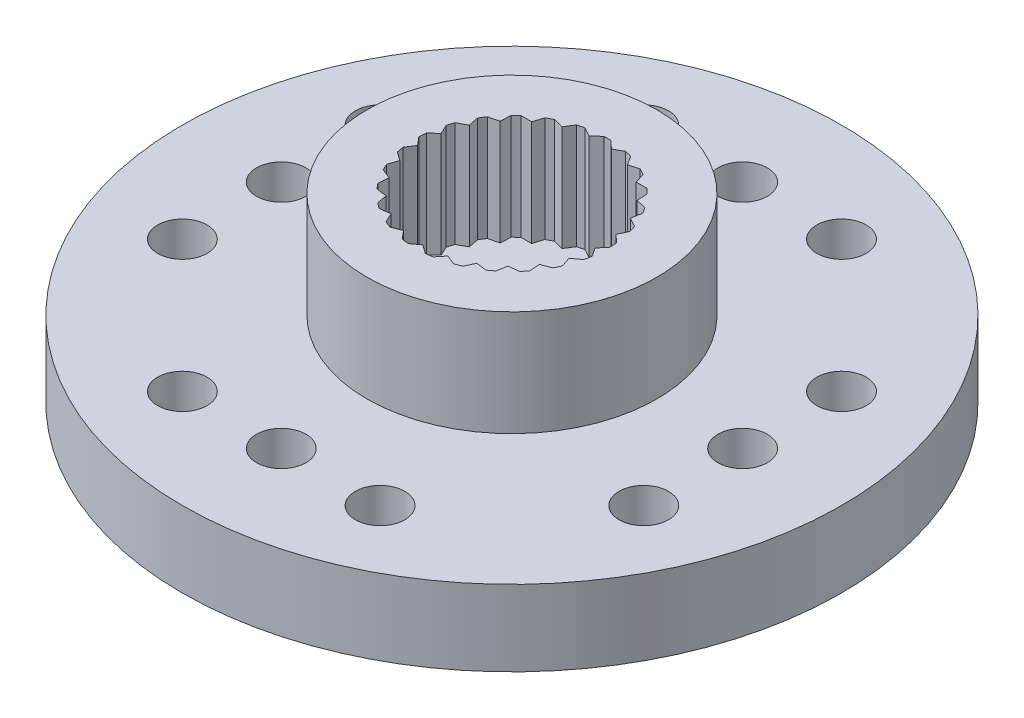
SolidWorks part; units mm, degrees
material "ABS"
ref_plane "Front Plane" through (0, 0, 0) normal (0, 0, 1) x (1, 0, 0)
ref_plane "Top Plane" through (0, 0, 0) normal (0, 1, 0) x (1, 0, 0)
ref_plane "Right Plane" through (0, 0, 0) normal (1, 0, 0) x (0, 0, -1)
sketch "Sketch2" plane through (0, 0, 0) normal (0, 1, 0) x (1, 0, 0)
  circle A0 centre (0, 0) radius 6
  circle A1 centre (0, 0) radius 1.5
  dimension "D1" = 12
  dimension "D2" = 3
extrude "Boss-Extrude1" add sketch "Sketch2" along normal mid plane 2.3
sketch "Sketch3" plane through (0, 1.15, 0) normal (0, 1, 0) x (1, 0, 0)
  line L0 (0, 0) -> (0, 2.9) construction
  line L3 (0, 0) -> (0.376, 2.9763) construction
  line L52 (0.1074, 2.898) -> (0.3384, 2.6787)
  line L53 (-0.1074, 2.898) -> (-0.3384, 2.6787)
  line L54 (0.8248, 2.7802) -> (0.9939, 2.5104)
  line L55 (0.6167, 2.8337) -> (0.3384, 2.6787)
  line L56 (1.4903, 2.4878) -> (1.587, 2.1843)
  line L57 (1.302, 2.5913) -> (0.9939, 2.5104)
  line L58 (2.0621, 2.039) -> (2.0804, 1.721)
  line L59 (1.9055, 2.1861) -> (1.587, 2.1843)
  line L60 (2.5044, 1.4621) -> (2.443, 1.1496)
  line L61 (2.3893, 1.6435) -> (2.0804, 1.721)
  line L62 (2.7894, 0.7934) -> (2.6522, 0.5059)
  line L63 (2.723, 0.9977) -> (2.443, 1.1496)
  line L64 (2.899, 0.0748) -> (2.6947, -0.1695)
  line L65 (2.8855, 0.2892) -> (2.6522, 0.5059)
  line L66 (2.8265, -0.6486) -> (2.5679, -0.8343)
  line L67 (2.8668, -0.4375) -> (2.6947, -0.1695)
  line L68 (2.5765, -1.3311) -> (2.2797, -1.4467)
  line L69 (2.6679, -1.1367) -> (2.5679, -0.8343)
  line L70 (2.1645, -1.93) -> (1.8483, -1.9682)
  line L71 (2.3014, -1.7645) -> (2.2797, -1.4467)
  line L72 (1.6165, -2.4077) -> (1.3007, -2.366)
  line L73 (1.7903, -2.2814) -> (1.8483, -1.9682)
  line L74 (0.967, -2.734) -> (0.6715, -2.6152)
  line L75 (1.1667, -2.655) -> (1.3007, -2.366)
  line L76 (0.2566, -2.8886) -> (0, -2.7)
  line L77 (0.4698, -2.8617) -> (0.6715, -2.6152)
  line L78 (-0.4698, -2.8617) -> (-0.6715, -2.6152)
  line L79 (-0.2566, -2.8886) -> (0, -2.7)
  line L80 (-1.1667, -2.655) -> (-1.3007, -2.366)
  line L81 (-0.967, -2.734) -> (-0.6715, -2.6152)
  line L82 (-1.7903, -2.2814) -> (-1.8483, -1.9682)
  line L83 (-1.6165, -2.4077) -> (-1.3007, -2.366)
  line L84 (-2.3014, -1.7645) -> (-2.2797, -1.4467)
  line L85 (-2.1645, -1.93) -> (-1.8483, -1.9682)
  line L86 (-2.6679, -1.1367) -> (-2.5679, -0.8343)
  line L87 (-2.5765, -1.3311) -> (-2.2797, -1.4467)
  line L88 (-2.8668, -0.4375) -> (-2.6947, -0.1695)
  line L89 (-2.8265, -0.6486) -> (-2.5679, -0.8343)
  line L90 (-2.8855, 0.2892) -> (-2.6522, 0.5059)
  line L91 (-2.899, 0.0748) -> (-2.6947, -0.1695)
  line L92 (-2.723, 0.9977) -> (-2.443, 1.1496)
  line L93 (-2.7894, 0.7934) -> (-2.6522, 0.5059)
  line L94 (-2.3893, 1.6435) -> (-2.0804, 1.721)
  line L95 (-2.5044, 1.4621) -> (-2.443, 1.1496)
  line L96 (-1.9055, 2.1861) -> (-1.587, 2.1843)
  line L97 (-2.0621, 2.039) -> (-2.0804, 1.721)
  line L98 (-1.302, 2.5913) -> (-0.9939, 2.5104)
  line L99 (-1.4903, 2.4878) -> (-1.587, 2.1843)
  line L100 (-0.6167, 2.8337) -> (-0.3384, 2.6787)
  line L101 (-0.8248, 2.7802) -> (-0.9939, 2.5104)
  line L102 (-2.533, 1.6075) -> (-2.3893, 1.6435) construction
  line L103 (-2.533, 1.6075) -> (-2.5044, 1.4621) construction
  line L104 (-2.8532, 0.9271) -> (-2.723, 0.9977) construction
  line L105 (-2.8532, 0.9271) -> (-2.7894, 0.7934) construction
  line L106 (-2.9941, 0.1884) -> (-2.8855, 0.2892) construction
  line L107 (-2.9941, 0.1884) -> (-2.899, 0.0748) construction
  line L108 (-2.9469, -0.5621) -> (-2.8668, -0.4375) construction
  line L109 (-2.9469, -0.5621) -> (-2.8265, -0.6486) construction
  line L110 (0, 3) -> (0.1074, 2.898) construction
  line L111 (0, 2.9) -> (0, 3) construction
  line L112 (0, 3) -> (-0.1074, 2.898) construction
  line L113 (-0.7461, 2.9057) -> (-0.6167, 2.8337) construction
  line L114 (-0.7461, 2.9057) -> (-0.8248, 2.7802) construction
  line L115 (-1.4453, 2.6289) -> (-1.302, 2.5913) construction
  line L116 (-1.4453, 2.6289) -> (-1.4903, 2.4878) construction
  line L117 (-2.0536, 2.1869) -> (-1.9055, 2.1861) construction
  line L118 (-2.0536, 2.1869) -> (-2.0621, 2.039) construction
  line L119 (-2.7145, -1.2773) -> (-2.6679, -1.1367) construction
  line L120 (-2.7145, -1.2773) -> (-2.5765, -1.3311) construction
  line L121 (-2.3115, -1.9123) -> (-2.3014, -1.7645) construction
  line L122 (-2.3115, -1.9123) -> (-2.1645, -1.93) construction
  line L123 (-1.7634, -2.4271) -> (-1.7903, -2.2814) construction
  line L124 (-1.7634, -2.4271) -> (-1.6165, -2.4077) construction
  line L125 (-1.1044, -2.7893) -> (-1.1667, -2.655) construction
  line L126 (-1.1044, -2.7893) -> (-0.967, -2.734) construction
  line L127 (-0.376, -2.9763) -> (-0.4698, -2.8617) construction
  line L128 (-0.376, -2.9763) -> (-0.2566, -2.8886) construction
  line L129 (0.376, -2.9763) -> (0.2566, -2.8886) construction
  line L130 (0.376, -2.9763) -> (0.4698, -2.8617) construction
  line L131 (1.1044, -2.7893) -> (0.967, -2.734) construction
  line L132 (1.1044, -2.7893) -> (1.1667, -2.655) construction
  line L133 (1.7634, -2.4271) -> (1.6165, -2.4077) construction
  line L134 (1.7634, -2.4271) -> (1.7903, -2.2814) construction
  line L135 (2.3115, -1.9123) -> (2.3014, -1.7645) construction
  line L136 (2.3115, -1.9123) -> (2.1645, -1.93) construction
  line L137 (2.7145, -1.2773) -> (2.6679, -1.1367) construction
  line L138 (2.7145, -1.2773) -> (2.5765, -1.3311) construction
  line L139 (2.9469, -0.5621) -> (2.8668, -0.4375) construction
  line L140 (2.9469, -0.5621) -> (2.8265, -0.6486) construction
  line L141 (2.9941, 0.1884) -> (2.8855, 0.2892) construction
  line L142 (2.9941, 0.1884) -> (2.899, 0.0748) construction
  line L143 (2.8532, 0.9271) -> (2.723, 0.9977) construction
  line L144 (2.8532, 0.9271) -> (2.7894, 0.7934) construction
  line L145 (2.533, 1.6075) -> (2.3893, 1.6435) construction
  line L146 (2.533, 1.6075) -> (2.5044, 1.4621) construction
  line L147 (2.0536, 2.1869) -> (1.9055, 2.1861) construction
  line L148 (2.0536, 2.1869) -> (2.0621, 2.039) construction
  line L149 (1.4453, 2.6289) -> (1.302, 2.5913) construction
  line L150 (1.4453, 2.6289) -> (1.4903, 2.4878) construction
  line L151 (0.7461, 2.9057) -> (0.6167, 2.8337) construction
  line L152 (0.7461, 2.9057) -> (0.8248, 2.7802) construction
  circle A0 centre (0, 0) radius 4.4
  circle A1 centre (0, 0) radius 3 construction
  circle A2 centre (0, 0) radius 2.7 construction
  arc A3 (-0.6167, 2.8337) -> (-0.8248, 2.7802) centre (0, 0) ccw
  arc A4 (-0.1074, 2.898) -> (-0.6167, 2.8337) centre (0, 0) ccw construction
  arc A5 (-0.8248, 2.7802) -> (-1.302, 2.5913) centre (0, 0) ccw construction
  arc A6 (-1.302, 2.5913) -> (-1.4903, 2.4878) centre (0, 0) ccw
  arc A7 (-1.4903, 2.4878) -> (-1.9055, 2.1861) centre (0, 0) ccw construction
  arc A8 (-1.9055, 2.1861) -> (-2.0621, 2.039) centre (0, 0) ccw
  arc A9 (-2.0621, 2.039) -> (-2.3893, 1.6435) centre (0, 0) ccw construction
  arc A10 (-2.3893, 1.6435) -> (-2.5044, 1.4621) centre (0, 0) ccw
  arc A11 (-2.5044, 1.4621) -> (-2.723, 0.9977) centre (0, 0) ccw construction
  arc A12 (-2.723, 0.9977) -> (-2.7894, 0.7934) centre (0, 0) ccw
  arc A13 (-2.7894, 0.7934) -> (-2.8855, 0.2892) centre (0, 0) ccw construction
  arc A14 (-2.8855, 0.2892) -> (-2.899, 0.0748) centre (0, 0) ccw
  arc A15 (-2.899, 0.0748) -> (-2.8668, -0.4375) centre (0, 0) ccw construction
  arc A16 (-2.8668, -0.4375) -> (-2.8265, -0.6486) centre (0, 0) ccw
  arc A17 (-2.8265, -0.6486) -> (-2.6679, -1.1367) centre (0, 0) ccw construction
  arc A18 (-2.6679, -1.1367) -> (-2.5765, -1.3311) centre (0, 0) ccw
  arc A19 (-2.5765, -1.3311) -> (-2.3014, -1.7645) centre (0, 0) ccw construction
  arc A20 (-2.3014, -1.7645) -> (-2.1645, -1.93) centre (0, 0) ccw
  arc A21 (-2.1645, -1.93) -> (-1.7903, -2.2814) centre (0, 0) ccw construction
  arc A22 (-1.7903, -2.2814) -> (-1.6165, -2.4077) centre (0, 0) ccw
  arc A23 (-1.6165, -2.4077) -> (-1.1667, -2.655) centre (0, 0) ccw construction
  arc A24 (-1.1667, -2.655) -> (-0.967, -2.734) centre (0, 0) ccw
  arc A25 (-0.967, -2.734) -> (-0.4698, -2.8617) centre (0, 0) ccw construction
  arc A26 (-0.4698, -2.8617) -> (-0.2566, -2.8886) centre (0, 0) ccw
  arc A27 (-0.2566, -2.8886) -> (0.2566, -2.8886) centre (0, 0) ccw construction
  arc A28 (0.2566, -2.8886) -> (0.4698, -2.8617) centre (0, 0) ccw
  arc A29 (0.4698, -2.8617) -> (0.967, -2.734) centre (0, 0) ccw construction
  arc A30 (0.967, -2.734) -> (1.1667, -2.655) centre (0, 0) ccw
  arc A31 (1.1667, -2.655) -> (1.6165, -2.4077) centre (0, 0) ccw construction
  arc A32 (1.6165, -2.4077) -> (1.7903, -2.2814) centre (0, 0) ccw
  arc A33 (1.7903, -2.2814) -> (2.1645, -1.93) centre (0, 0) ccw construction
  arc A34 (2.1645, -1.93) -> (2.3014, -1.7645) centre (0, 0) ccw
  arc A35 (2.3014, -1.7645) -> (2.5765, -1.3311) centre (0, 0) ccw construction
  arc A36 (2.5765, -1.3311) -> (2.6679, -1.1367) centre (0, 0) ccw
  arc A37 (2.6679, -1.1367) -> (2.8265, -0.6486) centre (0, 0) ccw construction
  arc A38 (2.8265, -0.6486) -> (2.8668, -0.4375) centre (0, 0) ccw
  arc A39 (2.8668, -0.4375) -> (2.899, 0.0748) centre (0, 0) ccw construction
  arc A40 (2.899, 0.0748) -> (2.8855, 0.2892) centre (0, 0) ccw
  arc A41 (2.8855, 0.2892) -> (2.7894, 0.7934) centre (0, 0) ccw construction
  arc A42 (2.7894, 0.7934) -> (2.723, 0.9977) centre (0, 0) ccw
  arc A43 (2.723, 0.9977) -> (2.5044, 1.4621) centre (0, 0) ccw construction
  arc A44 (2.5044, 1.4621) -> (2.3893, 1.6435) centre (0, 0) ccw
  arc A45 (2.3893, 1.6435) -> (2.0621, 2.039) centre (0, 0) ccw construction
  arc A46 (2.0621, 2.039) -> (1.9055, 2.1861) centre (0, 0) ccw
  arc A47 (1.9055, 2.1861) -> (1.4903, 2.4878) centre (0, 0) ccw construction
  arc A48 (1.4903, 2.4878) -> (1.302, 2.5913) centre (0, 0) ccw
  arc A49 (1.302, 2.5913) -> (0.8248, 2.7802) centre (0, 0) ccw construction
  arc A50 (0.8248, 2.7802) -> (0.6167, 2.8337) centre (0, 0) ccw
  arc A51 (0.3635, 2.8771) -> (0.1074, 2.898) centre (0, 0) ccw construction
  arc A52 (0.1074, 2.898) -> (-0.1074, 2.898) centre (0, 0) ccw
  arc A53 (0.6167, 2.8337) -> (0.3635, 2.8771) centre (0, 0) ccw construction
  point P84 (0, 0)
  dimension "D1" = 8.8
  dimension "D2" = 5.4
  dimension "D3" = 6
  dimension "D6" = 5.8
  dimension "D4" = 7.2
  dimension "D5" = 25
extrude "Boss-Extrude2" add sketch "Sketch3" along normal blind 3.2
sketch "Sketch4" plane through (0, 0, 0) normal (0, 1, 0) x (1, 0, 0)
  line L0 (0, 0) -> (13, 0) construction
  line L1 (3.9686, 4.5) -> (14.0007, 2.4494)
  line L2 (3.9686, -4.5) -> (14.0007, -2.4494)
  line L3 (13, 0) -> (10, 0) construction
  circle A0 centre (0, 0) radius 6 construction
  arc A1 (3.9686, -4.5) -> (3.9686, 4.5) centre (0, 0) ccw
  arc A2 (14.0007, 2.4494) -> (14.0007, -2.4494) centre (13.5, 0) cw
  circle A3 centre (13, 0) radius 0.75
  circle A4 centre (10, 0) radius 0.75
  circle A5 centre (7, 0) radius 0.75
  dimension "D3" = 2.5
  dimension "D5" = 1.5
  dimension "D2" = 9
  dimension "D7" = 3
  dimension "D4" = 0.5
extrude "Boss-Extrude3" [suppressed] add sketch "Sketch4" along normal mid plane 2.3
pattern_circular "CirPattern1" [suppressed] count 6 over 360 of bodies 103
sketch "Sketch5" plane through (0, 0, 0) normal (0, 1, 0) x (1, 0, 0)
  line L0 (3, 7) -> (-3, 7) construction
  circle A0 centre (0, 0) radius 10
  circle A1 centre (0, 7) radius 0.75
  circle A2 centre (-3, 7) radius 0.75
  circle A3 centre (3, 7) radius 0.75
  circle A4 centre (7, 3) radius 0.75
  circle A5 centre (7, 0) radius 0.75
  circle A6 centre (7, -3) radius 0.75
  circle A7 centre (3, -7) radius 0.75
  circle A8 centre (0, -7) radius 0.75
  circle A9 centre (-3, -7) radius 0.75
  circle A10 centre (-7, -3) radius 0.75
  circle A11 centre (-7, 0) radius 0.75
  circle A12 centre (-7, 3) radius 0.75
  circle A13 centre (0, 0) radius 1.5 construction
  circle A14 centre (0, 0) radius 1.5
  point P8 (0, 7)
  point P31 (0, 0)
  dimension "D1" = 1.5
  dimension "D3" = 2.25
  dimension "D4" = 6
  dimension "D2" = 7
  dimension "D5" = 4
extrude "Boss-Extrude4" add sketch "Sketch5" along normal mid plane 2.3
equation "\"N_hole\"= 3"
equation "\"N_horn\"= 6"
equation "\"D6@Sketch4\"=\"N_hole\""
equation "\"D1@CirPattern1\"=\"N_horn\""
equation "\"D1@Sketch4\"=(\"N_hole\" - 1) *3 +7"
